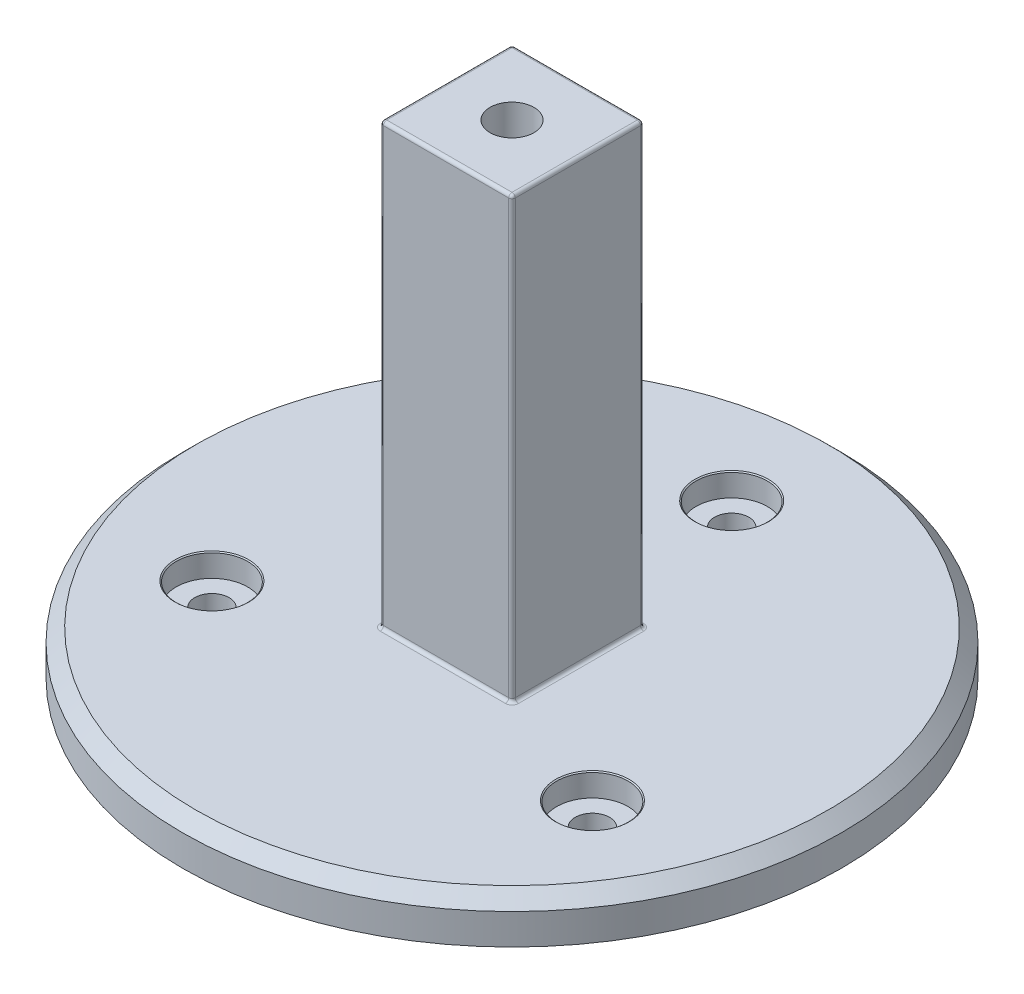
SolidWorks part; units mm, degrees
material "C-Glass Fiber"
ref_plane "Front Plane" through (0, 0, 0) normal (0, 0, 1) x (1, 0, 0)
ref_plane "Top Plane" through (0, 0, 0) normal (0, 1, 0) x (1, 0, 0)
ref_plane "Right Plane" through (0, 0, 0) normal (1, 0, 0) x (0, 0, -1)
sketch "Sketch1" plane through (0, 0, 0) normal (0, 1, 0) x (1, 0, 0)
  circle A0 centre (0, 0) radius 190.5
  dimension "D1" = 381
extrude "Boss-Extrude1" add sketch "Sketch1" along normal blind 25.4
chamfer "Chamfer1" distance 7.62 angle 45 1 edges at (0, 25.4, 190.5)
ref_axis "Axis1" through (0, -239.2144, 0) along (0, 1, 0)
sketch "Sketch2" plane through (0, 25.4, 0) normal (0, 1, 0) x (1, 0, 0)
  line L1 (-38.1, -38.1) -> (38.1, -38.1)
  line L2 (-38.1, -38.1) -> (-38.1, 38.1)
  line L3 (-38.1, 38.1) -> (38.1, 38.1)
  line L4 (38.1, -38.1) -> (38.1, 38.1)
  line L5 (-38.1, -38.1) -> (38.1, 38.1) construction
  line L6 (-38.1, 38.1) -> (38.1, -38.1) construction
  point P0 (0, 0)
  dimension "D1" = 76.2
  dimension "D2" = 76.2
extrude "Boss-Extrude2" add sketch "Sketch2" along normal blind 254
hole_wizard "CBORE for 3/4 Hex Head Bolt1" positions "Sketch13" profile "Sketch14" counterbore size "3/4" standard "ANSI Inch" end condition up to next
sketch "Sketch13" plane through (0, 25.4, 0) normal (0, 1, 0) x (1, 0, 0)
  point P0 (0, 127)
  dimension "D1" = 127
sketch "Sketch14" plane through (0, 25.4, -127) normal (1, 0, 0) x (0, 0, 1)
  line L0 (0, 0) -> (0, 25.401)
  line L1 (0, 25.401) -> (9.9212, 25.401)
  line L3 (9.9212, 25.401) -> (9.9212, 13.3096)
  line L4 (20.6375, 13.3096) -> (9.9212, 13.3096)
  line L5 (20.6375, 13.3096) -> (20.6375, 0.5328)
  line L6 (20.6375, 0.5328) -> (21.2725, 0)
  line L7 (21.2725, 0) -> (0, 0)
  line L8 (-20.6375, 0.5328) -> (-21.2725, 0) construction
  line L11 (0, -6.35) -> (0, 107.95) construction
  dimension "Thru Hole Dia." = 19.8425
  dimension "Thru Hole Depth" = 25.401
  dimension "C'Bore Dia." = 41.275
  dimension "C'Bore Depth" = 13.3096
  dimension "Near C'Sink Dia." = 42.545
  dimension "Near C'Sink Angle" = 100
pattern_circular "CirPattern1" count 3 over 360 about axis through (0, -239.2144, 0) along (0, 1, 0) of "CBORE for 3/4 Hex Head Bolt1"
hole_wizard "Hole1" positions "Sketch15" profile "Sketch16" legacy
sketch "Sketch15" plane through (0, 279.4, 0) normal (0, 1, 0) x (1, 0, 0)
  point P0 (0, 0)
sketch "Sketch16" plane through (0, 279.4, 0) normal (1, 0, 0) x (0, 0, 1)
  line L0 (0, 0) -> (0, 253.999)
  line L1 (0, 253.999) -> (12.7, 253.999)
  line L2 (12.7, 253.999) -> (12.7, 0)
  line L3 (12.7, 0) -> (0, 0)
  line L4 (0, 110) -> (0, -10) construction
  dimension "Diameter" = 25.4
  dimension "Depth" = 253.999
fillet "Fillet1" radius 1.905 12 edges at (38.1, 152.4, 38.1) (-38.1, 152.4, 38.1) (38.1, 279.4, 0) (0, 279.4, 38.1) (-38.1, 279.4, 0) (0, 279.4, -38.1) (38.1, 152.4, -38.1) (-38.1, 152.4, -38.1) (0, 25.4, -38.1) (-38.1, 25.4, 0) (38.1, 25.4, 0) (0, 25.4, 38.1)
